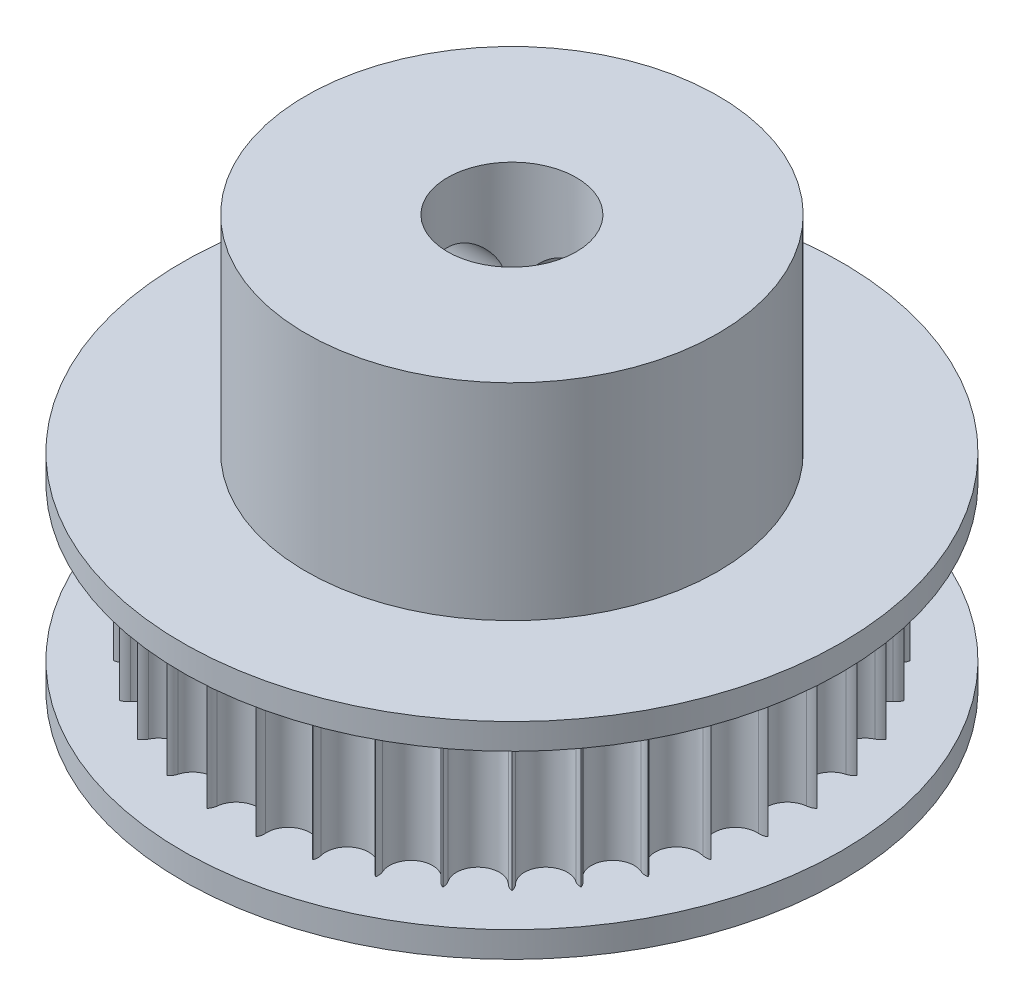
SolidWorks part; units mm, degrees
ref_plane "Front plan" through (0, 0, 0) normal (0, 0, 1) x (1, 0, 0)
ref_plane "Top plan" through (0, 0, 0) normal (0, 1, 0) x (1, 0, 0)
ref_plane "Right plan" through (0, 0, 0) normal (1, 0, 0) x (0, 0, -1)
sketch "Skica2" plane through (0, 0, 0) normal (0, 0, 1) x (1, 0, 0)
  line L0 (8, 8.5) -> (2.5, 8.5)
  line L1 (2.5, 8.5) -> (2.5, -8.5)
  line L2 (2.5, -8.5) -> (6.11, -8.5)
  line L3 (0, -8.5) -> (0, 8.5) construction
  line L4 (0, 8.5) -> (2.5, 8.5)
  line L5 (0, -8.5) -> (2.5, -8.5)
  line L6 (6.11, -8.5) -> (6.11, -7.5)
  line L7 (12.8, -0.5) -> (11.15, -0.5)
  line L8 (11.15, -0.5) -> (11.15, -6.5)
  line L9 (12.8, -0.5) -> (12.8, 0.5)
  line L12 (12.8, -7.5) -> (6.11, -7.5)
  line L13 (12.8, 0.5) -> (8, 0.5)
  line L14 (12.8, -7.5) -> (12.8, -6.5)
  line L15 (11.15, -6.5) -> (12.8, -6.5)
  line L16 (8, 0.5) -> (8, 8.5)
  point P6 (9.455, -7.5)
  point P7 (0, 0)
  dimension "D2" = 1
  dimension "D6" = 25.6
  dimension "D3" = 22.3
  dimension "D1" = 5
  dimension "D8" = 17
  dimension "D4" = 1
  dimension "D7" = 16
  dimension "D9" = 8
revolve "Revolute" add sketch "Skica2" angle 360 about L3 region at (6.3138, -0.7046, 0)
sketch "Sketch2" plane through (0, -0.5, 0) normal (0, -1, 0) x (1, 0, 0)
  line L0 (0, 0) -> (0, 10.7023) construction
  line L1 (0, 0) -> (3.7597, 10.497) construction
  line L3 (0, 0) -> (-2.1589, 10.939) construction
  circle A1 centre (0, 0) radius 9.8663 construction
  circle A2 centre (0, 0) radius 10.65 construction
  arc A3 (-0.8317, 10.6175) -> (0.8317, 10.6175) centre (0, 10.7023) ccw
  arc A7 (-1.3915, 11.0628) -> (-2.1589, 10.939) centre (0, 0) ccw
  arc A8 (0, 12.5893) -> (2.1589, 10.939) centre (0.5977, 11.134) cw
  circle A9 centre (0, 0) radius 11.15 construction
  arc A10 (1.3915, 11.0628) -> (2.1589, 10.939) centre (0, 0) cw
  arc A11 (1.3915, 11.0628) -> (0.8317, 10.6175) centre (1.3291, 10.5667) ccw
  arc A12 (0, 12.5893) -> (-2.1589, 10.939) centre (-0.5977, 11.134) ccw
  arc A13 (-1.3915, 11.0628) -> (-0.8317, 10.6175) centre (-1.3291, 10.5667) cw
  circle M8 centre (0, 0) radius 11.15
  dimension "D2" = 1
  dimension "D4" = 0.836
  dimension "D6" = 22.3
  dimension "D3" = 1.5733
extrude "Cut-Extrude1" cut sketch "Sketch2" along normal up to surface (6 mm away) contours A8 M8 | A11 A3 M8 region at (0, -0.5, 10.6043) region at (0, -0.5, 11.8034) up to face at (12.8, -6.5, 0)
pattern_circular "CirPattern1" count 36 over 360 about axis through (0, -8.5, 0) along (0, -1, 0) of "Cut-Extrude1" reverse direction yes
sketch "Sketch3" plane through (0, 0, 0) normal (1, 0, 0) x (0, 0, -1)
  line L0 (0, 8.5) -> (0, 0.5) construction
  line L1 (2.5, 8.5) -> (-2.5, 8.5) construction
  circle A0 centre (0, 4.5) radius 1.65
  dimension "D1" = 3.3
extrude "Cut-Extrude2" cut sketch "Sketch3" against normal up to next
sketch "Sketch4" plane through (0, 0, 0) normal (0, 0, 1) x (1, 0, 0)
  line L0 (0, 8.5) -> (0, -0.5) construction
  line L1 (12.8, 8.5) -> (-12.8, 8.5) construction
  line L2 (-0.8317, -0.5) -> (0.8317, -0.5) construction
  circle A0 centre (0, 4) radius 1.65
  dimension "D1" = 3.3
extrude "Cut-Extrude3" cut sketch "Sketch4" against normal up to next
chamfer "Chamfer1" distance 1 angle 45 1 edges at (6.11, -7.5, 0)
sketch "Sketch5" plane through (0, 8.5, 0) normal (0, 1, 0) x (1, 0, 0)
  line L0 (0, -16.03) -> (0, 16.03) construction
  point P6 (0, 0)
equation "\"`\"=2"
equation "\"D6@Sketch2\"= \"D3@Skica2\""
